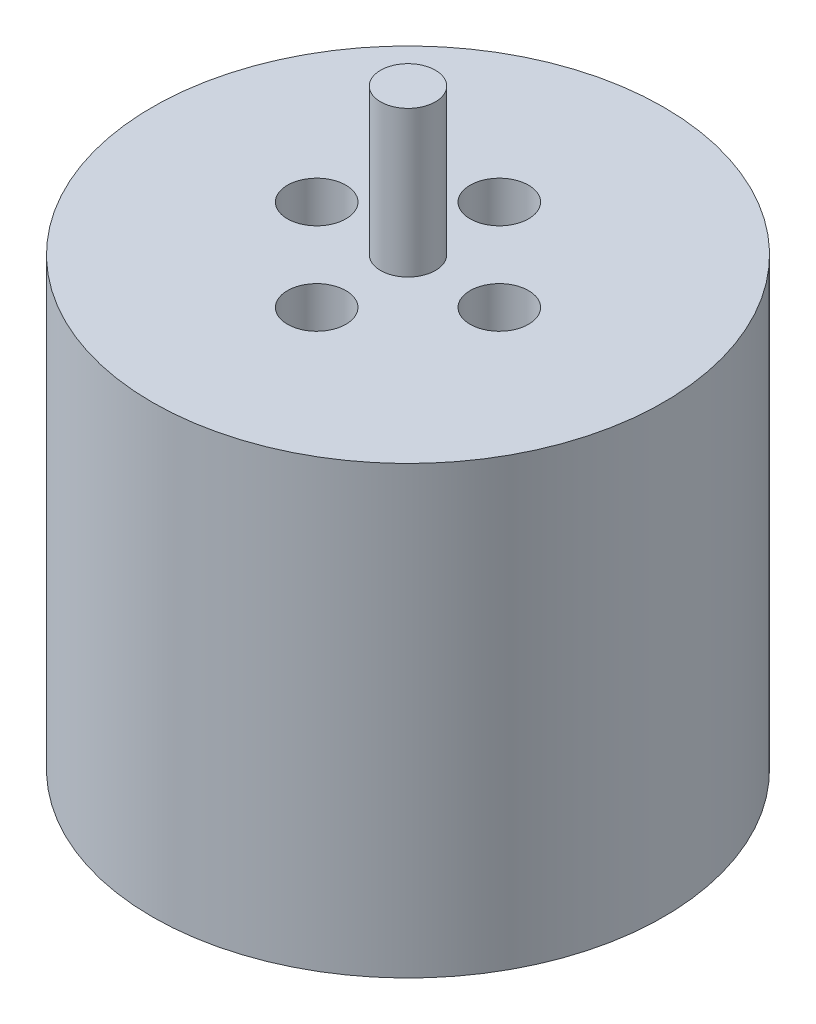
SolidWorks part; units mm, degrees
ref_plane "Front Plane" through (0, 0, 0) normal (0, 0, 1) x (1, 0, 0)
ref_plane "Top Plane" through (0, 0, 0) normal (0, 1, 0) x (1, 0, 0)
ref_plane "Right Plane" through (0, 0, 0) normal (1, 0, 0) x (0, 0, -1)
sketch "Sketch1" plane through (0, 0, 0) normal (0, 1, 0) x (1, 0, 0)
  circle A0 centre (0, 0) radius 7
  dimension "D1" = 14
extrude "Boss-Extrude1" add sketch "Sketch1" along normal mid plane 12.2
sketch "Sketch2" plane through (0, -6.1, 0) normal (0, -1, 0) x (1, 0, 0)
  circle A0 centre (0, 0) radius 0.75
  dimension "D1" = 1.5
extrude "Boss-Extrude2" add sketch "Sketch2" along normal blind 1
sketch "Sketch3" plane through (0, 6.1, 0) normal (0, 1, 0) x (1, 0, 0)
  circle A0 centre (0, 0) radius 0.75
  dimension "D1" = 1.5
extrude "Boss-Extrude3" add sketch "Sketch3" along normal blind 4
sketch "Sketch4" plane through (0, -6.1, 0) normal (0, -1, 0) x (1, 0, 0)
  circle A0 centre (0, 4.5) radius 0.8
  circle A1 centre (4.5, 0) radius 0.8
  circle A2 centre (0, -4.5) radius 0.8
  circle A3 centre (-4.5, 0) radius 0.8
  dimension "D1" = 1.6
  dimension "D2" = 9
  dimension "D3" = 9
  dimension "D4" = 4.5
  dimension "D5" = 4.5
extrude "Cut-Extrude1" cut sketch "Sketch4" against normal blind 2
sketch "Sketch5" plane through (0, 6.1, 0) normal (0, 1, 0) x (1, 0, 0)
  circle A0 centre (2.5, 0) radius 0.8
  circle A1 centre (0, -2.5) radius 0.8
  circle A2 centre (-2.5, 0) radius 0.8
  circle A3 centre (0, 2.5) radius 0.8
  circle A4 centre (0, 0) radius 2.5 construction
  dimension "D1" = 1.6
  dimension "D2" = 5
extrude "Cut-Extrude2" cut sketch "Sketch5" against normal blind 2
equation "\"D3@Sketch4\"=\"D2@Sketch4\""
equation "\"D4@Sketch4\"=\"D2@Sketch4\"/2"
equation "\"D5@Sketch4\"=\"D4@Sketch4\""
